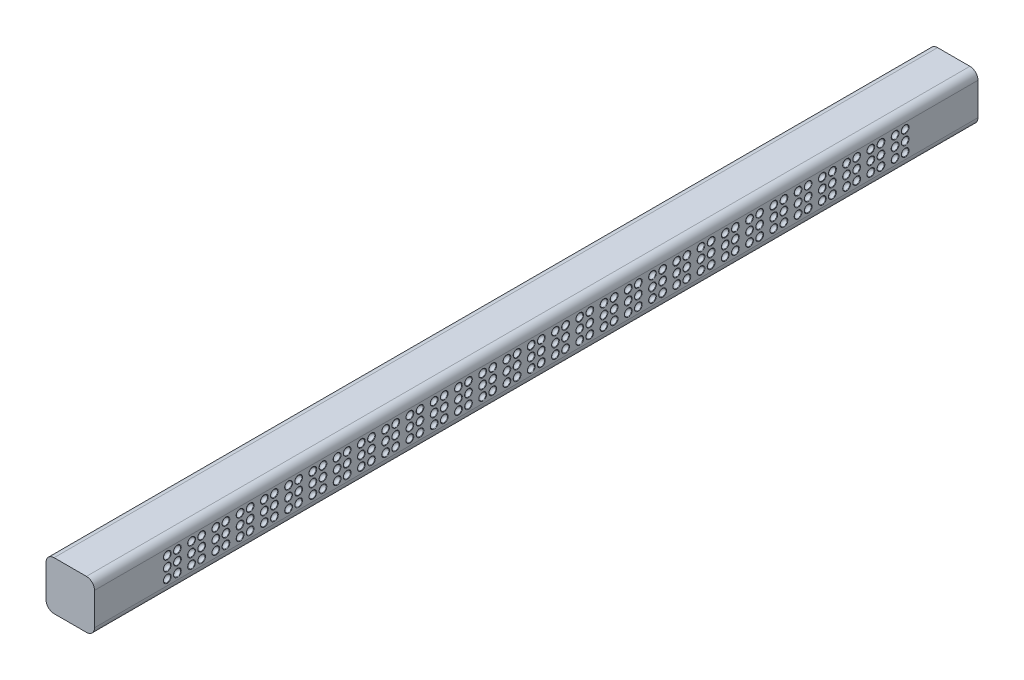
SolidWorks part; units mm, degrees
ref_plane "Front plane" through (0, 0, 0) normal (0, 0, 1) x (1, 0, 0)
ref_plane "Top plane" through (0, 0, 0) normal (0, 1, 0) x (1, 0, 0)
ref_plane "Right Plane" through (0, 0, 0) normal (1, 0, 0) x (0, 0, -1)
sketch "Sketch2" plane through (0, 0, 0) normal (0, 0, 1) x (1, 0, 0)
  line L1 (-4, 6) -> (4, 6)
  line L2 (-6, 4) -> (-6, -4)
  line L3 (-4, -6) -> (4, -6)
  line L4 (6, 4) -> (6, -4)
  arc A0 (-4, 6) -> (-6, 4) centre (-4, 4) ccw
  arc A1 (4, 6) -> (6, 4) centre (4, 4) cw
  arc A2 (4, -6) -> (6, -4) centre (4, -4) ccw
  arc A3 (-6, -4) -> (-4, -6) centre (-4, -4) ccw
  point P8 (6, 0)
  point P16 (0, 6)
  dimension "D3" = 2
  dimension "D1" = 12
extrude "Boss-Extrude1" add sketch "Sketch2" along normal blind 218.5
sketch "Sketch3" plane through (6, 0, 0) normal (1, 0, 0) x (0, 0, -1)
  line L0 (-20.5, -2.5) -> (-20.5, 0) construction
  line L1 (-20.5, -2.5) -> (-18, -2.5) construction
  line L2 (0, -4) -> (0, 4) construction
  circle A0 centre (-20.5, -2.5) radius 0.875
  circle A1 centre (-18, -2.5) radius 0.875
  circle A2 centre (-18, 0) radius 0.875
  circle A3 centre (-18, 2.5) radius 0.875
  circle A4 centre (-20.5, 0) radius 0.875
  circle A5 centre (-20.5, 2.5) radius 0.875
  point P3 (-19.25, -2.5)
  dimension "D5" = 1.75
  dimension "D3" = 2.5
  dimension "D4" = 2.5
  dimension "D6" = 19.25
  dimension "D1" = 2
  dimension "D2" = 3
extrude "Cut-Extrude1" cut sketch "Sketch3" against normal blind 1
chamfer "Chamfer1" [suppressed] distance 0.875 angle 30
fillet "Fillet1" radius 0.875 6 edges at (5, 2.5, 17.125) (5, 2.5, 19.625) (5, 0, 19.625) (5, 0, 17.125) (5, -2.5, 17.125) (5, -2.5, 19.625)
fillet "Fillet2" radius 0.1 6 edges at (6, -2.5, 17.125) (6, -2.5, 19.625) (6, 0, 19.625) (6, 2.5, 19.625) (6, 2.5, 17.125) (6, 0, 17.125)
pattern_linear "LPattern2" [suppressed] count 31 spacing 6 of bodies 103
pattern_linear "LPattern1" count 31 spacing 6 along (0, 0, 1) of "Cut-Extrude1", "Fillet2", "Fillet1"
